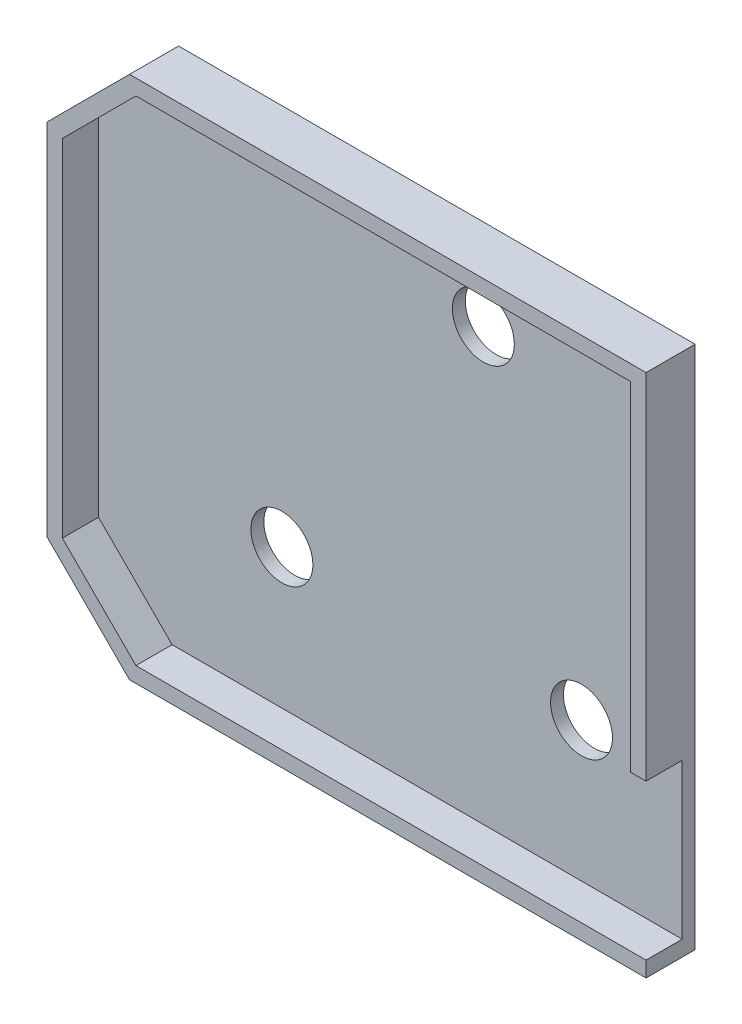
SolidWorks part; units mm, degrees
ref_plane "Plan de face" through (0, 0, 0) normal (0, 0, 1) x (1, 0, 0)
ref_plane "Plan de dessus" through (0, 0, 0) normal (0, 1, 0) x (1, 0, 0)
ref_plane "Plan de droite" through (0, 0, 0) normal (1, 0, 0) x (0, 0, -1)
sketch "Esquisse1" plane through (0, 0, 0) normal (0, 0, 1) x (1, 0, 0)
  line L0 (0, -85) -> (16, -101)
  line L4 (116, 0.5) -> (116, -101)
  line L5 (16, 0.5) -> (0, -15.5)
  line L7 (116, 0.5) -> (16, 0.5)
  line L8 (0, -15.5) -> (0, -85)
  line L9 (16, -101) -> (116, -101)
  dimension "D1" = 101.5
  dimension "D2" = 116
  dimension "D3" = 16
  dimension "D4" = 16
  dimension "D5" = 16
  dimension "D6" = 16
extrude "Boss.-Extru.1" add sketch "Esquisse1" along normal blind 2.5
sketch "Esquisse2" plane through (0, 0, 2.5) normal (0, 0, 1) x (1, 0, 0)
  line L0 (0, -15.5) -> (0, -85) construction
  line L1 (3, -2.5) -> (113, -2.5) construction
  line L2 (3, -2.5) -> (3, -98) construction
  line L3 (3, -98) -> (113, -98) construction
  line L4 (113, -2.5) -> (113, -98) construction
  line L5 (16, -101) -> (116, -101) construction
  line L6 (116, -101) -> (116, 0.5) construction
  line L7 (116, 0.5) -> (16, 0.5) construction
  line L9 (3, -83.7574) -> (17.2426, -98)
  line L10 (0, -85) -> (16, -101) construction
  line L11 (3, -16.7426) -> (17.2426, -2.5)
  line L12 (16, 0.5) -> (0, -15.5) construction
  line L13 (113, -2.5) -> (17.2426, -2.5)
  line L14 (3, -16.7426) -> (3, -83.7574)
  line L15 (17.2426, -98) -> (113, -98)
  line L16 (116, 0.5) -> (116, -101) construction
  line L17 (116, -101) -> (16, -101)
  line L18 (16, -101) -> (0, -85)
  line L19 (0, -85) -> (0, -15.5)
  line L20 (0, -15.5) -> (16, 0.5)
  line L21 (16, 0.5) -> (116, 0.5)
  line L30 (116, -2.5) -> (116, 0.5)
  line L31 (113, -98) -> (116, -98)
  line L32 (116, -98) -> (116, -101)
  line L33 (113, -2.5) -> (113, -68)
  line L34 (113, -68) -> (116, -68)
  line L35 (116, -68) -> (116, -2.5)
  point P24 (114.5, -98)
  dimension "D1" = 3
  dimension "D2" = 3
  dimension "D3" = 3
  dimension "D4" = 3
  dimension "D5" = 3
  dimension "D6" = 3
  dimension "D7" = 30
extrude "Boss.-Extru.2" add sketch "Esquisse2" along normal blind 7
sketch "Esquisse3" plane through (0, 0, 2.5) normal (0, 0, 1) x (1, 0, 0)
  line L0 (116, -98) -> (17.2426, -98) construction
  line L1 (17.2426, -2.5) -> (113, -2.5) construction
  line L2 (113, -2.5) -> (113, -68) construction
  line L3 (3, -83.7574) -> (3, -16.7426) construction
  circle A0 centre (96.5, -71) radius 6
  circle A1 centre (77.5, -14.5) radius 6
  circle A2 centre (38.5, -71) radius 6
  dimension "D1" = 27
  dimension "D2" = 27
  dimension "D3" = 12
  dimension "D4" = 16.5
  dimension "D5" = 35.5
  dimension "D6" = 35.5
extrude "Enlèv. mat.-Extru.1" cut sketch "Esquisse3" against normal blind 10
